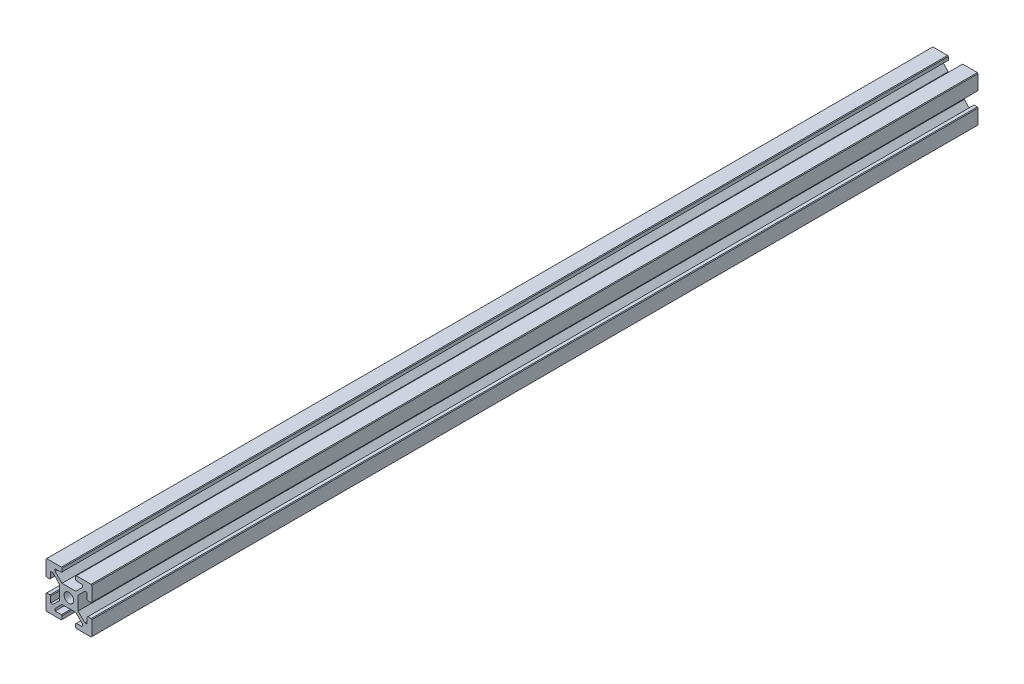
SolidWorks part; units mm, degrees
ref_plane "Front" through (0, 0, 0) normal (0, 0, 1) x (1, 0, 0)
ref_plane "Top" through (0, 0, 0) normal (0, 1, 0) x (1, 0, 0)
ref_plane "Right" through (0, 0, 0) normal (1, 0, 0) x (0, 0, -1)
sketch "Sketch1" plane through (0, 0, 0) normal (0, 0, 1) x (1, 0, 0)
  line L0 (-3, 10) -> (3, 10)
  line L1 (-10, 10) -> (10, 10)
  line L2 (-10, 10) -> (-10, -10)
  line L3 (-10, -10) -> (10, -10)
  line L4 (10, 10) -> (10, -10)
  line L5 (-10, 10) -> (10, -10) construction
  line L6 (-10, -10) -> (10, 10) construction
  line L7 (3, 10) -> (3, 8)
  line L8 (3, 8) -> (6, 8)
  line L9 (-3, 4) -> (3, 4)
  line L10 (0, -11) -> (0, 11) construction
  line L11 (3, 4) -> (6, 7)
  line L12 (6, 7) -> (6, 8)
  line L13 (10, 3) -> (10, -3)
  line L14 (-3, 10) -> (-3, 8)
  line L15 (-3, 8) -> (-6, 8)
  line L16 (-6, 7) -> (-6, 8)
  line L17 (-3, 4) -> (-6, 7)
  line L18 (10, -3) -> (8, -3)
  line L19 (8, -3) -> (8, -6)
  line L20 (7, -6) -> (8, -6)
  line L21 (4, -3) -> (7, -6)
  line L22 (4, 3) -> (4, -3)
  line L23 (4, 3) -> (7, 6)
  line L24 (7, 6) -> (8, 6)
  line L25 (8, 3) -> (8, 6)
  line L26 (10, 3) -> (8, 3)
  line L27 (3, -10) -> (-3, -10)
  line L28 (-3, -10) -> (-3, -8)
  line L29 (-3, -8) -> (-6, -8)
  line L30 (-6, -7) -> (-6, -8)
  line L31 (-3, -4) -> (-6, -7)
  line L32 (3, -4) -> (-3, -4)
  line L33 (3, -4) -> (6, -7)
  line L34 (6, -7) -> (6, -8)
  line L35 (3, -8) -> (6, -8)
  line L36 (3, -10) -> (3, -8)
  line L37 (-10, -3) -> (-10, 3)
  line L38 (-10, 3) -> (-8, 3)
  line L39 (-8, 3) -> (-8, 6)
  line L40 (-7, 6) -> (-8, 6)
  line L41 (-4, 3) -> (-7, 6)
  line L42 (-4, -3) -> (-4, 3)
  line L43 (-4, -3) -> (-7, -6)
  line L44 (-7, -6) -> (-8, -6)
  line L45 (-8, -3) -> (-8, -6)
  line L46 (-10, -3) -> (-8, -3)
  circle A0 centre (0, 0) radius 2.1
  point P0 (0, 0)
  point P18 (0, 10)
  point P22 (0, 4)
  point P53 (0, 0)
  dimension "D1" = 20
  dimension "D2" = 20
  dimension "D3" = 3
  dimension "D4" = 2
  dimension "D5" = 3
  dimension "D6" = 6
  dimension "D7" = 3
  dimension "D8" = 4
extrude "Boss-Extrude1" add sketch "Sketch1" along normal blind 387.35 contours L46 L2 L3 L28 L29 L30 L31 L32 L33 L34 L35 L36 L4 L18 L19 L20 L21 L22 L23 L24 L25 L26 L1 L7 L8 L12 L11 L9 L17 L16 L15 L14 L38 L39 L40 L41 L42 L43 L44 L45 A0 region at (-3.2828, 9, 0)
chamfer "Chamfer1" distance 0.2828 angle 45 20 edges at (-8, 3, 193.675) (-3, 8, 193.675) (-3, 10, 193.675) (-10, 3, 193.675) (-10, 10, 193.675) (-8, -3, 193.675) (-10, -3, 193.675) (-10, -10, 193.675) (-3, -10, 193.675) (-3, -8, 193.675) (3, -8, 193.675) (3, -10, 193.675) (8, -3, 193.675) (10, -10, 193.675) (10, -3, 193.675) (8, 3, 193.675) (10, 3, 193.675) (10, 10, 193.675) (3, 8, 193.675) (3, 10, 193.675)
